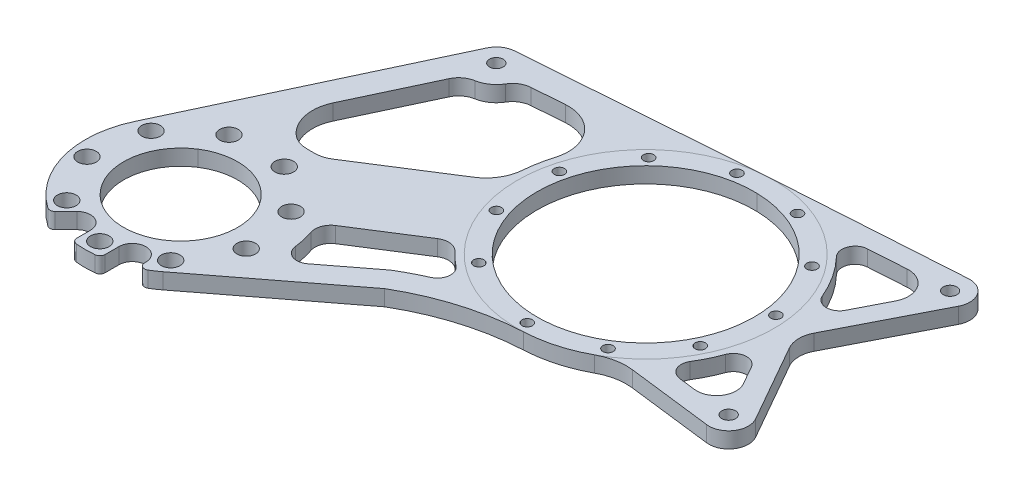
SolidWorks part; units mm, degrees
other "Markup2"
sketch "Sketch8" plane through (392.176, 9.525, 205.994) normal (0, 1, 0) x (-1, 0, 0)
other "Markup3"
sketch "Sketch9" plane through (392.176, 9.525, 4.4528) normal (0, 1, 0) x (-1, 0, 0)
material "6061-T6 (SS)"
ref_plane "X-Y Datum" through (0, 0, 0) normal (0, 0, 1) x (1, 0, 0)
ref_plane "X-Z Datum" through (0, 0, 0) normal (0, 1, 0) x (1, 0, 0)
ref_plane "Y-Z Datum" through (0, 0, 0) normal (1, 0, 0) x (0, 0, -1)
sketch "Sketch1" plane through (0, 0, 0) normal (0, 1, 0) x (-1, 0, 0)
  line L1 (-575.31, 72.8215) -> (-438.15, 160.02) construction
  line L2 (-663.3443, 5.1159) -> (-571.3342, 11.0368)
  line L3 (-568.96, 0) -> (-463.042, 0) construction
  line L4 (-575.31, 72.8215) -> (-463.042, 0) construction
  line L6 (-672.4346, 18.9616) -> (-648.7868, 65.1568)
  line L8 (-414.9501, 197.3367) -> (-420.215, 192.0718)
  line L9 (-431.3112, 196.668) -> (-431.3112, 203.2407)
  line L10 (-444.9888, 203.2407) -> (-444.9888, 196.668)
  line L11 (-457.9888, 196.668) -> (-457.9888, 197.245)
  line L12 (-685.8, 0) -> (-568.96, 0) construction
  line L13 (-685.8, 130.5733) -> (-685.8, 0) construction
  line L16 (-450.7361, 24.8976) -> (-396.5254, 140.5006)
  line L17 (-670.601, 115.0847) -> (-649.0541, 77.2258)
  line L18 (-526.6297, 150.1211) -> (-466.1201, 196.5067)
  line L20 (-508.2633, 125.1657) -> (-498.3912, 109.6373) construction
  line L21 (-503.8626, 118.2436) -> (-490.7147, 118.2436) construction
  line L22 (-698.5, 155.9733) -> (-673.1, 155.9733) construction
  line L23 (-698.5, 12.7) -> (-673.1, 12.7) construction
  line L24 (-698.5, 12.7) -> (-698.5, -12.7) construction
  line L25 (-698.5, -12.7) -> (-673.1, -12.7) construction
  line L26 (-673.1, 12.7) -> (-673.1, -12.7) construction
  line L27 (-698.5, 12.7) -> (-673.1, -12.7) construction
  line L28 (-698.5, -12.7) -> (-673.1, 12.7) construction
  line L29 (-698.5, 155.9733) -> (-698.5, 130.5733) construction
  line L30 (-698.5, 130.5733) -> (-673.1, 130.5733) construction
  line L31 (-673.1, 155.9733) -> (-673.1, 130.5733) construction
  line L32 (-698.5, 155.9733) -> (-673.1, 130.5733) construction
  line L33 (-698.5, 130.5733) -> (-673.1, 155.9733) construction
  line L35 (-661.162, 129.2501) -> (-620.2745, 124.2297)
  line L36 (-672.139, 129.6123) -> (-652.5065, 109.9799) construction
  line L37 (-463.042, 0) -> (-463.042, 3.81) construction
  line L38 (-570.7022, 11.0807) -> (-458.6511, 19.4431)
  line L40 (-575.31, 125.209) -> (-575.31, 134.734) construction
  circle A3 centre (-438.15, 199.02) radius 4.5 construction
  circle A4 centre (-438.15, 160.02) radius 39 construction
  circle A5 centre (-662.3228, 119.7961) radius 9.525 construction
  circle A6 centre (-663.956, 14.6213) radius 9.525 construction
  circle A7 centre (-459.36, 28.9417) radius 9.525 construction
  circle A8 centre (-438.15, 160.02) radius 27.4955
  arc A11 (-411.6923, 197.6179) -> (-396.5254, 140.5006) centre (-438.15, 160.02) cw
  arc A13 (-672.4346, 18.9616) -> (-663.3443, 5.1159) centre (-663.956, 14.6213) ccw
  arc A16 (-461.8375, 199.4219) -> (-411.6923, 197.6179) centre (-438.15, 160.02) ccw construction
  arc A17 (-411.6923, 197.6179) -> (-414.9501, 197.3367) centre (-413.1541, 195.5407) ccw
  arc A18 (-431.3112, 196.668) -> (-420.215, 192.0718) centre (-424.8112, 196.668) ccw
  arc A19 (-431.3112, 203.2407) -> (-433.5998, 205.7683) centre (-433.8512, 203.2407) ccw
  arc A20 (-433.5998, 205.7683) -> (-442.7002, 205.7683) centre (-438.15, 160.02) ccw
  arc A21 (-442.7002, 205.7683) -> (-444.9888, 203.2407) centre (-442.4488, 203.2407) ccw
  arc A22 (-457.9888, 196.668) -> (-444.9888, 196.668) centre (-451.4888, 196.668) ccw
  arc A23 (-457.9888, 197.245) -> (-461.8375, 199.4219) centre (-460.5288, 197.245) ccw
  arc A25 (-466.1201, 196.5067) -> (-461.8375, 199.4219) centre (-438.15, 160.02) cw
  arc A27 (-526.6297, 150.1211) -> (-578.3125, 134.6611) centre (-583.7676, 247.0155) cw
  circle A38 centre (-575.31, 72.8215) radius 61.9125 construction
  circle A39 centre (-575.31, 72.8215) radius 52.3875
  arc A40 (-604.9989, 127.1513) -> (-578.3125, 134.6611) centre (-575.31, 72.8215) cw
  arc A41 (-670.601, 115.0847) -> (-661.162, 129.2501) centre (-662.3228, 119.7961) cw
  circle A42 centre (-662.3228, 119.7961) radius 3.3
  circle A43 centre (-663.956, 14.6213) radius 3.3
  circle A44 centre (-459.36, 28.9417) radius 3.3
  arc A47 (-649.0541, 77.2258) -> (-648.7868, 65.1568) centre (-660.0917, 70.9439) cw
  arc A49 (-620.2745, 124.2297) -> (-604.9989, 127.1513) centre (-617.179, 149.4404) ccw
  arc A51 (-450.7361, 24.8976) -> (-458.6511, 19.4431) centre (-459.36, 28.9417) cw
  circle A53 centre (-463.042, 3.81) radius 12.7 construction
  arc A54 (-571.3342, 11.0368) -> (-570.7022, 11.0807) centre (-575.31, 72.8215) ccw
  circle A55 centre (-685.8, 0) radius 12.7 construction
  circle A56 centre (-685.8, 1.6598) radius 12.7 construction
  circle A58 centre (-575.31, 129.9715) radius 2.5 construction
  point P71 (-685.8, 143.2733)
  point P103 (-662.3228, 119.7961)
  point P105 (-611.3847, 123.1382)
  point P112 (-611.3847, 123.1382)
  dimension "D5" = 25.4
  dimension "D6" = 685.8
  dimension "D7" = 123.825
  dimension "D8" = 104.775
  dimension "D9" = 5
  dimension "D13" = 45.974
  dimension "D14" = 19.05
  dimension "D15" = 3.81
  dimension "D16" = 117.8733
  dimension "D19" = 25.4
  dimension "D20" = 9
  dimension "D21" = 3.682
  dimension "D18" = 6.5
  dimension "D23" = 78
  dimension "D24" = 25.4
  dimension "D35" = 25.4
  dimension "D22" = 54.991
  dimension "D26" = 12.7
  dimension "D38" = 112.4868
  dimension "D41" = 6.6
  dimension "D42" = 32.446
  dimension "D43" = 21.844
  dimension "D34" = 38
  dimension "D36" = 1.6598
  dimension "D2" = 222.758
  dimension "D3" = 247.65
  dimension "D4" = 160.02
  dimension "D10" = 575.31
  dimension "D11" = 72.8215
  dimension "D12" = 116.84
  dimension "D17" = 25.4
  dimension "D25" = 22.3788
  dimension "D33" = 15.354
  dimension "D37" = 25.4
  dimension "D39" = 9.8989
  dimension "D40" = 88.4797
  dimension "D44" = 72.8215
  dimension "D46" = 10.7772
  dimension "D47" = 10.7772
extrude "Boss-Extrude1" add sketch "Sketch1" along normal mid plane 7.62
hole_wizard "M8 Clearance Hole1" positions "Sketch5" profile "Sketch4" hole size "M8" standard "ANSI Metric" end condition through all
sketch "Sketch5" plane through (0, -3.81, 0) normal (0, -1, 0) x (-1, 0, 0)
  point P0 (-438.15, -199.02)
sketch "Sketch4" plane through (438.15, -3.81, 199.02) normal (1, 0, 0) x (0, 0, -1)
  line L0 (0, 0) -> (0, 7.62)
  line L1 (0, 7.62) -> (4.5, 7.62)
  line L2 (4.5, 7.62) -> (4.5, 0.025)
  line L3 (4.5, 0.025) -> (4.525, 0)
  line L5 (4.525, 0) -> (0, 0)
  line L6 (-4.5, 0.025) -> (-4.525, 0) construction
  line L11 (0, -6.35) -> (0, 107.95) construction
  dimension "Thru Hole Dia." = 9
  dimension "Thru Hole Depth" = 7.62
  dimension "Near C'Sink Dia." = 9.05
  dimension "Near C'Sink Angle" = 90
pattern_circular "CirPattern1" count 9 over 360 about axis through (438.15, 3.81, 160.02) along (0, -1, 0) of "M8 Clearance Hole1" reverse direction yes
sketch "Sketch6" plane through (0, 3.81, 0) normal (0, 1, 0) x (1, 0, 0)
  circle A0 centre (575.31, -72.8215) radius 61.9125 construction
  circle A1 centre (575.31, -72.8215) radius 61.9125
split line "Split Line2"
ref_point "Point1"
ref_point "Point2"
ref_plane "Plane1" through (570.7022, 0, 11.0807) normal (-0.8439, 0, 0.5365) x (0.5365, 0, 0.8439)
ref_plane "Plane2" through (438.15, 0, 160.02) normal (-0.8439, 0, 0.5365) x (0.5365, 0, 0.8439)
split line "Split Line3"
split line "Split Line4"
ref_axis "Axis1" through (575.31, 3.81, 72.8215) along (0, -1, 0)
ref_axis "Axis2" through (438.15, 6.1381, 160.02) along (0, -1, 0)
sketch "Sketch10" plane through (0, -3.81, 0) normal (0, -1, 0) x (1, 0, 0)
  line L0 (460.0554, 108.4708) -> (501.6535, 82.0251)
  line L1 (488.447, 135.5686) -> (518.5458, 116.4335)
  line L2 (462.2346, 30.2897) -> (408.0239, 145.8927)
  line L3 (454.4908, 46.8032) -> (436.5907, 84.9748)
  line L4 (449.5579, 110.4533) -> (453.2418, 110.4533)
  line L5 (575.31, 72.8215) -> (438.15, 160.02) construction
  line L9 (571.6474, 23.7455) -> (459.5963, 32.1079)
  line L13 (493.2983, 29.5927) -> (477.7847, 30.7505)
  line L18 (621.4353, 114.7757) -> (662.3228, 119.7961)
  line L21 (635.4204, 116.4929) -> (643.5069, 117.4858)
  line L23 (662.3228, 119.7961) -> (640.7759, 81.9372)
  line L25 (459.3594, 187.6874) -> (520.3915, 140.9012)
  line L26 (497.6765, 158.3141) -> (520.3915, 140.9012)
  line L27 (652.9459, 103.3204) -> (647.8594, 94.3831)
  line L29 (663.956, 14.6213) -> (571.9458, 20.5421)
  line L30 (644.4387, 15.8772) -> (626.4578, 17.0343)
  line L32 (640.3082, 60.8165) -> (663.956, 14.6213)
  line L33 (646.8337, 48.0691) -> (655.0441, 32.0304)
  arc A2 (520.3915, 140.9012) -> (577.7736, 123.5617) centre (583.7676, 247.0155) ccw
  arc A3 (520.3915, 140.9012) -> (533.1241, 134.268) centre (583.7676, 247.0155) ccw
  arc A5 (528.0838, 117.6107) -> (518.5458, 116.4335) centre (522.6004, 122.8112) cw
  arc A8 (576.9868, 7.7556) -> (634.9392, 98.9125) centre (575.31, 72.8215) ccw
  arc A9 (634.9392, 98.9125) -> (576.9868, 7.7556) centre (575.31, 72.8215) ccw
  arc A10 (622.2829, 27.7667) -> (635.326, 47.633) centre (575.31, 72.8215) ccw
  arc A11 (534.5034, 123.5285) -> (528.0838, 117.6107) centre (575.31, 72.8215) ccw
  arc A15 (464.8252, 201.9791) -> (411.4748, 118.0609) centre (438.15, 160.02) ccw
  arc A16 (411.4748, 118.0609) -> (464.8252, 201.9791) centre (438.15, 160.02) ccw
  arc A18 (485.3303, 144.3309) -> (487.5094, 154.0385) centre (438.15, 160.02) ccw
  arc A23 (436.5907, 84.9748) -> (440.9969, 107.134) centre (453.8385, 93.0629) cw
  arc A24 (533.1241, 134.268) -> (534.5034, 123.5285) centre (530.5222, 128.4755) cw
  arc A25 (487.5094, 154.0385) -> (497.6765, 158.3141) centre (493.8133, 153.2745) cw
  arc A26 (485.3303, 144.3309) -> (488.447, 135.5686) centre (492.5016, 141.9463) ccw
  arc A28 (510.4195, 67.5045) -> (512.9593, 54.0749) centre (575.31, 72.8215) ccw
  arc A29 (501.6535, 82.0251) -> (510.4195, 67.5045) centre (491.4332, 65.9488) cw
  arc A33 (470.2935, 35.4031) -> (461.5056, 41.4592) centre (459.36, 28.9417) ccw
  arc A34 (454.4908, 46.8032) -> (461.5056, 41.4592) centre (463.1147, 50.8473) ccw
  arc A39 (460.0554, 108.4708) -> (453.2418, 110.4533) centre (453.2418, 97.7533) ccw
  arc A40 (440.9969, 107.134) -> (449.5579, 110.4533) centre (449.5579, 97.7533) cw
  arc A48 (636.3823, 95.3283) -> (630.7823, 106.8686) centre (575.31, 72.8215) ccw
  arc A49 (643.5069, 117.4858) -> (652.9459, 103.3204) centre (644.6677, 108.0318) cw
  arc A50 (644.4387, 15.8772) -> (655.0441, 32.0304) centre (645.1523, 26.9668) ccw
  arc A51 (646.8337, 48.0691) -> (635.326, 47.633) centre (641.1813, 45.1756) ccw
  arc A52 (622.2829, 27.7667) -> (626.4578, 17.0343) centre (626.8656, 23.3712) ccw
  arc A53 (647.8594, 94.3831) -> (636.3823, 95.3283) centre (642.3406, 97.5241) cw
  arc A54 (630.7823, 106.8686) -> (635.4204, 116.4929) centre (636.1943, 110.1902) cw
  arc A55 (493.2983, 29.5927) -> (512.9593, 54.0749) centre (494.716, 48.5899) ccw
  arc A56 (470.2935, 35.4031) -> (477.7847, 30.7505) centre (478.4936, 40.2491) ccw
  point P14 (664.5919, 13.9778)
  point P78 (663.9188, 4.4766)
  point P79 (466.5721, 18.457)
  point P81 (467.2452, 27.9582)
  point P82 (664.8163, 17.1448)
  point P83 (467.4696, 31.1253)
  point P84 (664.5919, 13.9778)
  point P85 (467.2452, 27.9582)
  point P90 (639.9456, 80.4782)
  dimension "D5" = 12.7
  dimension "D10" = 19.05
  dimension "D11" = 9.525
  dimension "D13" = 9.525
  dimension "D14" = 9.525
  dimension "D15" = 9.525
  dimension "D16" = 9.525
  dimension "D17" = 19.05
  dimension "D18" = 6.35
  dimension "D21" = 7.5574
  dimension "D22" = 12.7
  dimension "D23" = 19.05
  dimension "D24" = 11.1125
  dimension "D3" = 25.4
  dimension "D4" = 9.525
  dimension "D20" = 12.7
  dimension "D27" = 6.35
  dimension "D29" = 65.1079
  dimension "D12" = 9.525
  dimension "D26" = 6.35
  dimension "D9" = 12.7
  dimension "D19" = 6.35
  dimension "D25" = 38.1
  dimension "D6" = 11.1125
  dimension "D7" = 12.7
  dimension "D8" = 22.225
extrude "Cut-Extrude2" cut sketch "Sketch10" against normal through all contours A28 A29 L0 L4 A23 L3 | A18 A26 L1 A5 A11 A24 A3 L26 A25 | A10 | A54 A48 A53 L27 A49 L21 region at (474.6259, -3.81, 68.5008) region at (509.2066, -3.81, 136.3659) region at (639.6623, -3.81, 30.5712) region at (642.3103, -3.81, 105.8185)
hole_wizard "Ø5.0mm Dowel Hole2" positions "Sketch13" profile "Sketch14" hole size "Ø5.0" standard "ANSI Metric"
sketch "Sketch13" plane through (0, 3.81, 0) normal (0, 1, 0) x (1, 0, 0)
  point P0 (575.31, -129.9715)
sketch "Sketch14" plane through (575.31, 3.81, 129.9715) normal (1, 0, 0) x (0, 0, 1)
  line L0 (0, 0) -> (0, 9.1222)
  line L1 (0, 9.1222) -> (2.5, 7.62)
  line L2 (2.5, 7.62) -> (2.5, 0)
  line L5 (2.5, 0) -> (0, 0)
  line L10 (0, 9.1222) -> (-2.5, 7.62) construction
  line L11 (0, -6.35) -> (0, 107.95) construction
  dimension "Hole Dia." = 5
  dimension "Hole Depth" = 7.62
  dimension "Drill Angle" = 118
pattern_circular "CirPattern3" count 11 every 32 about axis through (575.31, 3.81, 72.8215) along (0, -1, 0) of "Ø5.0mm Dowel Hole2" reverse direction yes
ref_point "Point3"
sketch "Sketch19" plane through (0, 3.81, 0) normal (0, 1, 0) x (1, 0, 0)
  line L0 (672.6753, -3.4704) -> (381.9838, -25.1649) construction
  line L1 (381.9838, -25.1649) -> (395.7251, -209.2881) construction
  line L3 (686.4165, -187.5936) -> (672.6753, -3.4704) construction
  line L4 (525.4487, -76.5427) -> (625.1713, -69.1003) construction
  line L5 (570.7022, -11.0807) -> (458.6511, -19.4431) construction
  line L6 (395.7251, -209.2881) -> (686.4165, -187.5936) construction
  line L7 (675.0192, -0.7484) -> (379.2618, -22.8209)
  line L8 (379.2618, -22.8209) -> (393.3811, -212.01)
  line L9 (393.3811, -212.01) -> (689.1385, -189.9375)
  line L10 (689.1385, -189.9375) -> (675.0192, -0.7484)
  line L11 (458.6927, -106.3273) -> (500.2908, -79.8816)
  line L12 (493.4873, -32.1257) -> (477.9738, -33.2835)
  line L13 (493.2983, -29.5927) -> (477.7847, -30.7505) construction
  line L14 (454.4908, -46.8032) -> (436.5907, -84.9748) construction
  line L15 (449.5579, -110.4533) -> (453.2418, -110.4533) construction
  line L16 (460.0554, -108.4708) -> (501.6535, -82.0251) construction
  line L17 (488.447, -135.5686) -> (518.5458, -116.4335) construction
  line L18 (497.6765, -158.3141) -> (520.3915, -140.9012) construction
  line L19 (644.4387, -15.8772) -> (626.4578, -17.0343) construction
  line L20 (646.8337, -48.0691) -> (655.0441, -32.0304) construction
  line L21 (652.9459, -103.3204) -> (647.8594, -94.3831) construction
  line L22 (635.4204, -116.4929) -> (643.5069, -117.4858) construction
  line L23 (493.2983, -29.5927) -> (477.7847, -30.7505) construction
  line L24 (454.4908, -46.8032) -> (436.5907, -84.9748) construction
  line L25 (449.5579, -110.4533) -> (453.2418, -110.4533) construction
  line L26 (460.0554, -108.4708) -> (501.6535, -82.0251) construction
  line L27 (488.447, -135.5686) -> (518.5458, -116.4335) construction
  line L28 (497.6765, -158.3141) -> (520.3915, -140.9012) construction
  line L29 (644.4387, -15.8772) -> (626.4578, -17.0343) construction
  line L30 (646.8337, -48.0691) -> (655.0441, -32.0304) construction
  line L31 (652.9459, -103.3204) -> (647.8594, -94.3831) construction
  line L32 (635.4204, -116.4929) -> (643.5069, -117.4858) construction
  line L33 (456.7905, -47.8816) -> (438.8904, -86.0532)
  line L34 (449.5579, -107.9133) -> (453.2418, -107.9133)
  line L35 (496.1312, -156.2983) -> (518.9623, -138.7964)
  line L36 (489.8097, -137.7121) -> (519.9085, -118.577)
  line L37 (650.7384, -104.5768) -> (645.6518, -95.6395)
  line L38 (635.7299, -113.9718) -> (643.8164, -114.9647)
  line L39 (644.5727, -46.9117) -> (652.7831, -30.873)
  line L40 (644.6018, -18.4119) -> (626.621, -19.569)
  line L41 (692.5986, 19.6666) -> (358.8469, -5.2415) construction
  line L42 (358.8469, -5.2415) -> (375.8017, -232.425) construction
  line L43 (375.8017, -232.425) -> (709.5535, -207.5169) construction
  line L44 (709.5535, -207.5169) -> (692.5986, 19.6666) construction
  arc A0 (396.5254, -140.5006) -> (411.6923, -197.6179) centre (438.15, -160.02) ccw construction
  arc A1 (433.5998, -205.7683) -> (442.7002, -205.7683) centre (438.15, -160.02) ccw construction
  arc A2 (672.4346, -18.9616) -> (663.3443, -5.1159) centre (663.956, -14.6213) ccw construction
  arc A3 (423.3986, -136.8166) -> (452.9014, -183.2234) centre (438.15, -160.02) ccw construction
  arc A4 (452.9014, -183.2234) -> (423.3986, -136.8166) centre (438.15, -160.02) ccw construction
  arc A5 (623.3042, -93.8216) -> (576.6596, -20.4514) centre (575.31, -72.8215) ccw construction
  arc A6 (576.6596, -20.4514) -> (623.3042, -93.8216) centre (575.31, -72.8215) ccw construction
  arc A7 (512.9593, -54.0749) -> (510.4195, -67.5045) centre (575.31, -72.8215) ccw construction
  arc A8 (512.9593, -54.0749) -> (493.2983, -29.5927) centre (494.716, -48.5899) ccw construction
  arc A9 (477.7847, -30.7505) -> (470.2935, -35.4031) centre (478.4936, -40.2491) ccw construction
  arc A10 (461.5056, -41.4592) -> (470.2935, -35.4031) centre (459.36, -28.9417) ccw construction
  arc A11 (461.5056, -41.4592) -> (454.4908, -46.8032) centre (463.1147, -50.8473) ccw construction
  arc A12 (436.5907, -84.9748) -> (440.9969, -107.134) centre (453.8385, -93.0629) ccw construction
  arc A13 (440.9969, -107.134) -> (449.5579, -110.4533) centre (449.5579, -97.7533) ccw construction
  arc A14 (453.2418, -110.4533) -> (460.0554, -108.4708) centre (453.2418, -97.7533) ccw construction
  arc A15 (501.6535, -82.0251) -> (510.4195, -67.5045) centre (491.4332, -65.9488) ccw construction
  arc A16 (528.0838, -117.6107) -> (534.5034, -123.5285) centre (575.31, -72.8215) ccw construction
  arc A17 (528.0838, -117.6107) -> (518.5458, -116.4335) centre (522.6004, -122.8112) ccw construction
  arc A18 (488.447, -135.5686) -> (485.3303, -144.3309) centre (492.5016, -141.9463) ccw construction
  arc A19 (487.5094, -154.0385) -> (485.3303, -144.3309) centre (438.15, -160.02) ccw construction
  arc A20 (487.5094, -154.0385) -> (497.6765, -158.3141) centre (493.8133, -153.2745) ccw construction
  arc A21 (533.1241, -134.268) -> (520.3915, -140.9012) centre (583.7676, -247.0155) ccw construction
  arc A22 (533.1241, -134.268) -> (534.5034, -123.5285) centre (530.5222, -128.4755) ccw construction
  arc A23 (635.326, -47.633) -> (622.2829, -27.7667) centre (575.31, -72.8215) ccw construction
  arc A24 (626.4578, -17.0343) -> (622.2829, -27.7667) centre (626.8656, -23.3712) ccw construction
  arc A25 (655.0441, -32.0304) -> (644.4387, -15.8772) centre (645.1523, -26.9668) ccw construction
  arc A26 (635.326, -47.633) -> (646.8337, -48.0691) centre (641.1813, -45.1756) ccw construction
  arc A27 (647.8594, -94.3831) -> (636.3823, -95.3283) centre (642.3406, -97.5241) ccw construction
  arc A28 (630.7823, -106.8686) -> (636.3823, -95.3283) centre (575.31, -72.8215) ccw construction
  arc A29 (630.7823, -106.8686) -> (635.4204, -116.4929) centre (636.1943, -110.1902) ccw construction
  arc A30 (643.5069, -117.4858) -> (652.9459, -103.3204) centre (644.6677, -108.0318) ccw construction
  arc A31 (423.3986, -136.8166) -> (452.9014, -183.2234) centre (438.15, -160.02) ccw construction
  arc A32 (452.9014, -183.2234) -> (423.3986, -136.8166) centre (438.15, -160.02) ccw construction
  arc A33 (623.3042, -93.8216) -> (576.6596, -20.4514) centre (575.31, -72.8215) ccw construction
  arc A34 (576.6596, -20.4514) -> (623.3042, -93.8216) centre (575.31, -72.8215) ccw construction
  arc A35 (512.9593, -54.0749) -> (510.4195, -67.5045) centre (575.31, -72.8215) ccw construction
  arc A36 (512.9593, -54.0749) -> (493.2983, -29.5927) centre (494.716, -48.5899) ccw construction
  arc A37 (477.7847, -30.7505) -> (470.2935, -35.4031) centre (478.4936, -40.2491) ccw construction
  arc A38 (461.5056, -41.4592) -> (470.2935, -35.4031) centre (459.36, -28.9417) ccw construction
  arc A39 (461.5056, -41.4592) -> (454.4908, -46.8032) centre (463.1147, -50.8473) ccw construction
  arc A40 (436.5907, -84.9748) -> (440.9969, -107.134) centre (453.8385, -93.0629) ccw construction
  arc A41 (440.9969, -107.134) -> (449.5579, -110.4533) centre (449.5579, -97.7533) ccw construction
  arc A42 (453.2418, -110.4533) -> (460.0554, -108.4708) centre (453.2418, -97.7533) ccw construction
  arc A43 (501.6535, -82.0251) -> (510.4195, -67.5045) centre (491.4332, -65.9488) ccw construction
  arc A44 (528.0838, -117.6107) -> (534.5034, -123.5285) centre (575.31, -72.8215) ccw construction
  arc A45 (528.0838, -117.6107) -> (518.5458, -116.4335) centre (522.6004, -122.8112) ccw construction
  arc A46 (488.447, -135.5686) -> (485.3303, -144.3309) centre (492.5016, -141.9463) ccw construction
  arc A47 (487.5094, -154.0385) -> (485.3303, -144.3309) centre (438.15, -160.02) ccw construction
  arc A48 (487.5094, -154.0385) -> (497.6765, -158.3141) centre (493.8133, -153.2745) ccw construction
  arc A49 (533.1241, -134.268) -> (520.3915, -140.9012) centre (583.7676, -247.0155) ccw construction
  arc A50 (533.1241, -134.268) -> (534.5034, -123.5285) centre (530.5222, -128.4755) ccw construction
  arc A51 (635.326, -47.633) -> (622.2829, -27.7667) centre (575.31, -72.8215) ccw construction
  arc A52 (626.4578, -17.0343) -> (622.2829, -27.7667) centre (626.8656, -23.3712) ccw construction
  arc A53 (655.0441, -32.0304) -> (644.4387, -15.8772) centre (645.1523, -26.9668) ccw construction
  arc A54 (635.326, -47.633) -> (646.8337, -48.0691) centre (641.1813, -45.1756) ccw construction
  arc A55 (647.8594, -94.3831) -> (636.3823, -95.3283) centre (642.3406, -97.5241) ccw construction
  arc A56 (630.7823, -106.8686) -> (636.3823, -95.3283) centre (575.31, -72.8215) ccw construction
  arc A57 (630.7823, -106.8686) -> (635.4204, -116.4929) centre (636.1943, -110.1902) ccw construction
  arc A58 (643.5069, -117.4858) -> (652.9459, -103.3204) centre (644.6677, -108.0318) ccw construction
  arc A59 (451.5387, -181.0799) -> (424.7613, -138.9601) centre (438.15, -160.02) ccw
  arc A60 (424.7613, -138.9601) -> (451.5387, -181.0799) centre (438.15, -160.02) ccw
  arc A61 (453.2418, -107.9133) -> (458.6927, -106.3273) centre (453.2418, -97.7533) ccw
  arc A62 (500.2908, -79.8816) -> (507.888, -67.2971) centre (491.4332, -65.9488) ccw
  arc A63 (510.5268, -53.3436) -> (507.888, -67.2971) centre (575.31, -72.8215) ccw
  arc A64 (510.5268, -53.3436) -> (493.4873, -32.1257) centre (494.716, -48.5899) ccw
  arc A65 (477.9738, -33.2835) -> (472.4802, -36.6953) centre (478.4936, -40.2491) ccw
  arc A66 (461.9347, -43.9627) -> (472.4802, -36.6953) centre (459.36, -28.9417) ccw
  arc A67 (461.9347, -43.9627) -> (456.7905, -47.8816) centre (463.1147, -50.8473) ccw
  arc A68 (438.8904, -86.0532) -> (442.7091, -105.2579) centre (453.8385, -93.0629) ccw
  arc A69 (442.7091, -105.2579) -> (449.5579, -107.9133) centre (449.5579, -97.7533) ccw
  arc A70 (490.0309, -153.7329) -> (496.1312, -156.2983) centre (493.8133, -153.2745) ccw
  arc A71 (532.0833, -131.951) -> (518.9623, -138.7964) centre (583.7676, -247.0155) ccw
  arc A72 (532.0833, -131.951) -> (532.9109, -125.5073) centre (530.5222, -128.4755) ccw
  arc A73 (526.2408, -119.3585) -> (532.9109, -125.5073) centre (575.31, -72.8215) ccw
  arc A74 (526.2408, -119.3585) -> (519.9085, -118.577) centre (522.6004, -122.8112) ccw
  arc A75 (489.8097, -137.7121) -> (487.7405, -143.5295) centre (492.5016, -141.9463) ccw
  arc A76 (490.0309, -153.7329) -> (487.7405, -143.5295) centre (438.15, -160.02) ccw
  arc A77 (576.5942, -22.9905) -> (620.9772, -92.8034) centre (575.31, -72.8215) ccw
  arc A78 (620.9772, -92.8034) -> (576.5942, -22.9905) centre (575.31, -72.8215) ccw
  arc A79 (643.8164, -114.9647) -> (650.7384, -104.5768) centre (644.6677, -108.0318) ccw
  arc A80 (645.6518, -95.6395) -> (638.7656, -96.2066) centre (642.3406, -97.5241) ccw
  arc A81 (632.9471, -108.1972) -> (638.7656, -96.2066) centre (575.31, -72.8215) ccw
  arc A82 (632.9471, -108.1972) -> (635.7299, -113.9718) centre (636.1943, -110.1902) ccw
  arc A83 (637.6681, -46.65) -> (644.5727, -46.9117) centre (641.1813, -45.1756) ccw
  arc A84 (652.7831, -30.873) -> (644.6018, -18.4119) centre (645.1523, -26.9668) ccw
  arc A85 (626.621, -19.569) -> (624.116, -26.0085) centre (626.8656, -23.3712) ccw
  arc A86 (637.6681, -46.65) -> (624.116, -26.0085) centre (575.31, -72.8215) ccw
  dimension "D2" = 2.54
  dimension "D1" = 2.54
  dimension "D3" = 19.05
extrude "Boss-Extrude2" [suppressed] add sketch "Sketch19" against normal blind 9.525 and the other way blind 3.175
ref_point "Point4"
